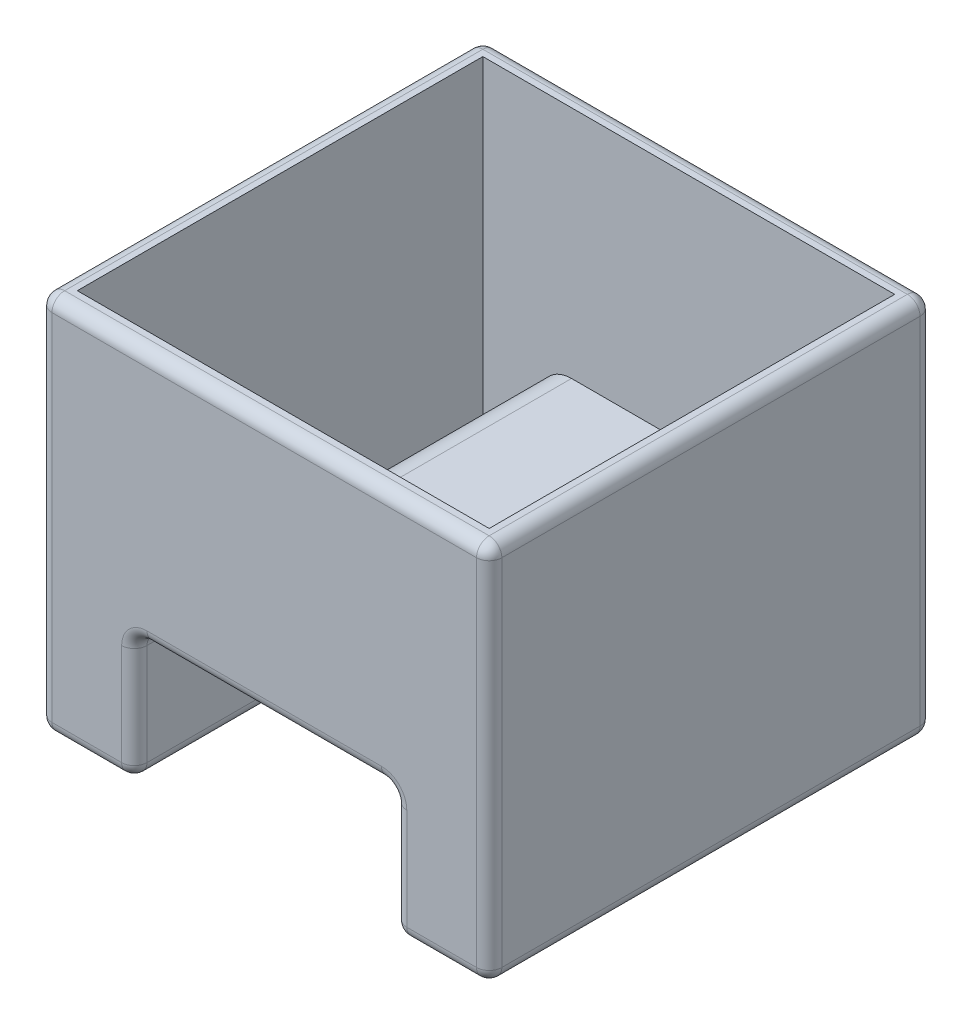
SolidWorks part; units mm, degrees
ref_plane "Face" through (0, 0, 0) normal (0, 0, 1) x (1, 0, 0)
ref_plane "Dessus" through (0, 0, 0) normal (0, 1, 0) x (1, 0, 0)
ref_plane "Droite" through (0, 0, 0) normal (1, 0, 0) x (0, 0, -1)
sketch "Esquisse2" plane through (0, 0, 0) normal (0, 0, 1) x (1, 0, 0)
  line L0 (-35.5, 0) -> (-20.5, 0)
  line L1 (-20.5, 0) -> (-20.5, 20)
  line L2 (-20.5, 20) -> (20.5, 20)
  line L3 (20.5, 20) -> (20.5, 0)
  line L4 (20.5, 0) -> (35.5, 0)
  line L5 (35.5, 0) -> (35.5, 60)
  line L6 (35.5, 60) -> (-35.5, 60)
  line L7 (-35.5, 60) -> (-35.5, 0)
  line L8 (0, -20) -> (0, 34.7572) construction
  line L9 (0, -40.5465) -> (0, 40.5465) construction
  line L12 (20, 3) -> (20, 0) construction
  line L13 (20, 3) -> (20, 0) construction
  point P12 (0, 20)
  point P13 (0, 34.7572)
  point P14 (0, 0)
  point P15 (0, 20)
  dimension "D1" = 0.5
  dimension "D2" = 60
  dimension "D3" = 20
extrude "Boss.-Extru.2" add sketch "Esquisse2" along normal blind 70
fillet "Congé4" radius 2 1 edges at (-35.5, 60, 35)
fillet "Congé3" radius 2 1 edges at (35.5, 60, 35)
fillet "Congé5" radius 2 1 edges at (20.5, 20, 35)
fillet "Congé6" radius 2 1 edges at (-20.5, 20, 35)
shell "Coque1" thickness 3 removed face at (0, 60, 35)
fillet "Congé7" radius 2 7 edges at (35.5, 29, 0) (34.9142, 59.4142, 0) (0, 60, 0) (-34.9142, 59.4142, 0) (-28, 0, 0) (-35.5, 0, 35) (-35.5, 29, 0)
fillet "Congé8" radius 2 24 edges at (-20.5, 9, 70) (-19.9142, 19.4142, 70) (19.9142, 19.4142, 70) (-34.9142, 0.5858, 70) (-34.9142, 59.4142, 70) (34.9142, 59.4142, 70) (-20.5, 0, 36) (-20.5, 0.5858, 0.5858) (-19.9142, 19.4142, 0) (19.9142, 19.4142, 0) (34.9142, 0, 0.5858) (0, 20, 70) (0, 20, 0) (-27, 0, 70) (-35.5, 30, 70) (0, 60, 70) (20.5, 9, 70) (28, 0, 70) (20.5, 0, 35) (35.5, 29, 70) (35.5, 0, 36) (-20.5, 10, 0) (20.5, 9, 0) (27, 0, 0)
